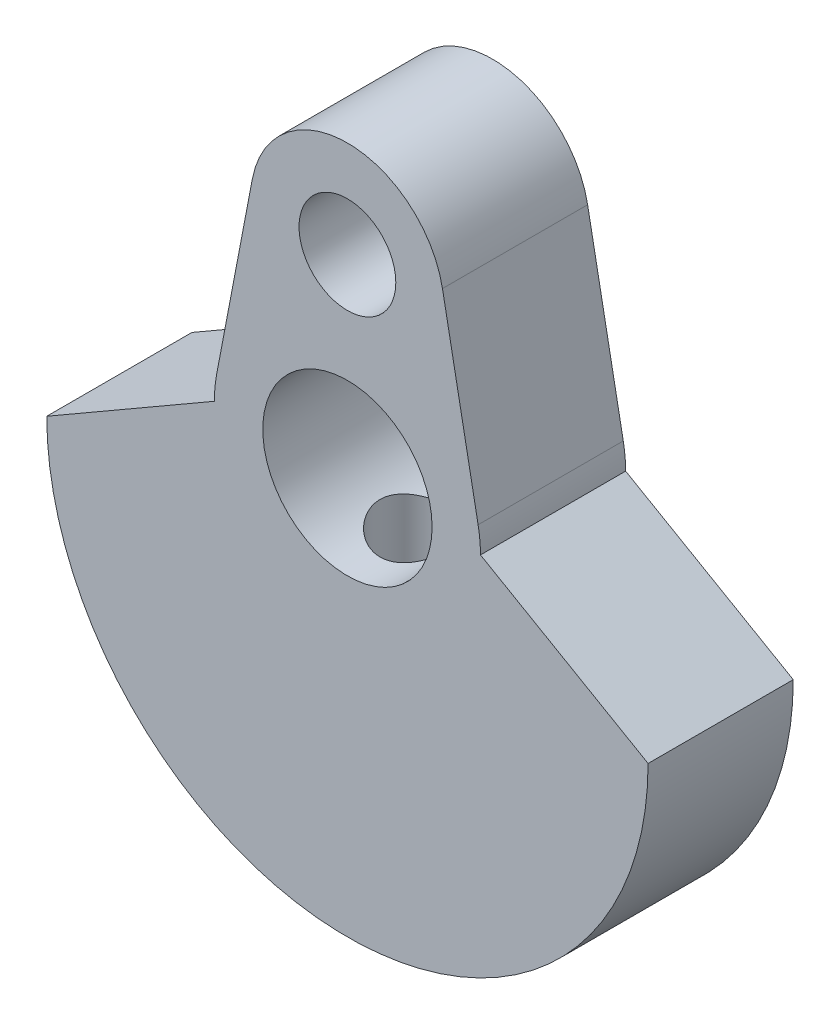
SolidWorks part; units mm, degrees
ref_plane "Front Plane" through (0, 0, 0) normal (0, 0, 1) x (1, 0, 0)
ref_plane "Top Plane" through (0, 0, 0) normal (0, 1, 0) x (1, 0, 0)
ref_plane "Right Plane" through (0, 0, 0) normal (1, 0, 0) x (0, 0, -1)
sketch "Sketch1" plane through (0, 0, 0) normal (0, 0, 1) x (1, 0, 0)
  line L0 (-11.3443, 0) -> (16.1311, 0) construction
  line L1 (-5.5, 0) -> (-12.4282, -4)
  line L2 (5.5, 0) -> (12.4282, -4)
  line L3 (5.4025, 1.0312) -> (3.9291, 8.75)
  line L4 (-5.4025, 1.0313) -> (-3.9291, 8.75)
  arc A0 (-12.4282, -4) -> (12.4282, -4) centre (0, -4) ccw
  circle A1 centre (0, 0) radius 5.5
  circle A2 centre (0, 0) radius 3.5
  circle A4 centre (0, 8) radius 2
  arc A5 (3.9291, 8.75) -> (-3.9291, 8.75) centre (0, 8) ccw
  dimension "D1" = 4
  dimension "D2" = 30
  dimension "D7" = 11
  dimension "D8" = 7
  dimension "D10" = 4
  dimension "D3" = 30
  dimension "D5" = 11
  dimension "D6" = 5.5
  dimension "D11" = 8
extrude "Boss-Extrude1" add sketch "Sketch1" along normal mid plane 6 contours A1 L1 A0 L2 | L3 A5 L4 A1 A4 region at (0, -8.6247, 0) region at (-4.5145, 4.8618, 0)
extrude "Boss-Extrude2" add sketch "Sketch1<3>" along normal mid plane 6 contours A1 L0 A2 | L0 A1 A2 region at (0, 3.623, 0) region at (4.5, -0.123, 0)
sketch "Sketch1<3>" plane through (0, 0, 0) normal (0, 0, 1) x (1, 0, 0) same geometry as "Sketch1"
ref_plane "Plane1" through (0, -16.4282, 0) normal (0, -1, 0) x (-1, 0, 0)
hole_wizard "M4 Tapped Hole1" positions "Sketch4" profile "Sketch5" tap size "M4" standard "DIN" end condition up to next
sketch "Sketch4" plane through (0, -16.4282, 0) normal (0, -1, 0) x (-1, 0, 0)
  point P0 (0, 0)
sketch "Sketch5" plane through (0, -16.4282, 0) normal (1, 0, 0) x (0, 0, -1)
  line L0 (0, 0) -> (0, 12.9282)
  line L1 (0, 12.9282) -> (1.65, 12.9282)
  line L2 (1.65, 12.9282) -> (1.65, 0)
  line L5 (1.65, 0) -> (0, 0)
  line L11 (0, -6.35) -> (0, 107.95) construction
  dimension "Thru Tap Drill Dia." = 3.3
  dimension "Thru Tap Drill Depth" = 12.9282
cosmetic thread "Hole Thread1"
